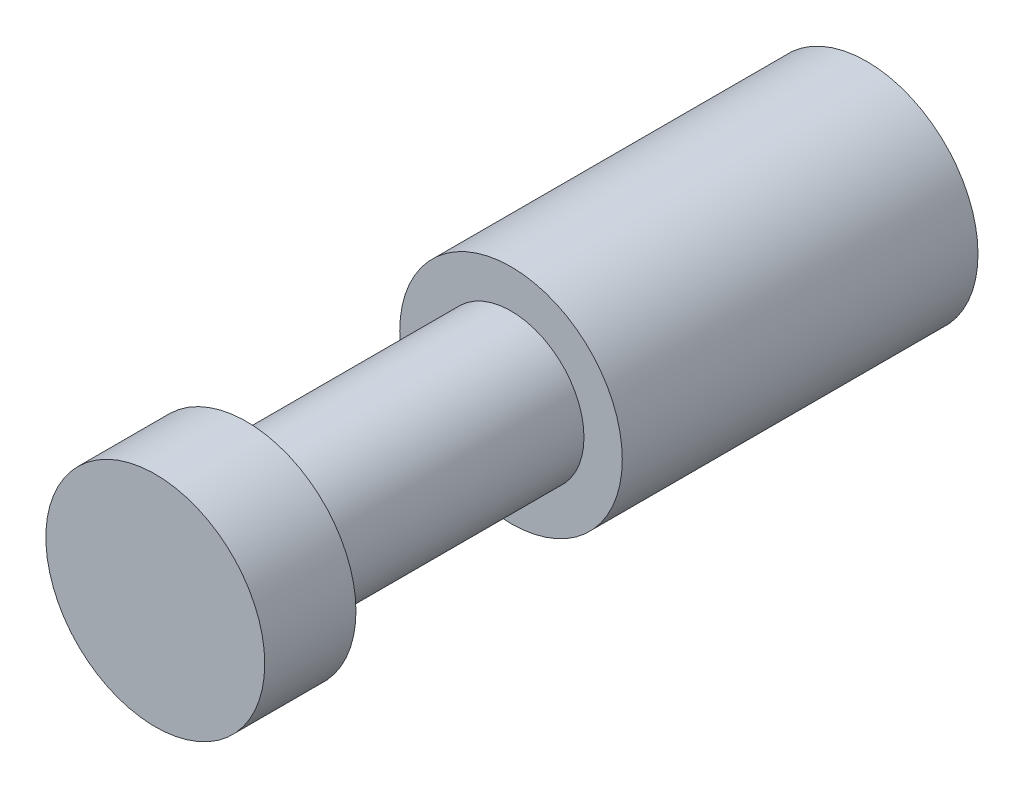
SolidWorks part; units mm, degrees
ref_plane "Front Plane" through (0, 0, 0) normal (0, 0, 1) x (1, 0, 0)
ref_plane "Top Plane" through (0, 0, 0) normal (0, 1, 0) x (1, 0, 0)
ref_plane "Right Plane" through (0, 0, 0) normal (1, 0, 0) x (0, 0, -1)
sketch "Sketch1" plane through (0, 0, 0) normal (0, 0, 1) x (1, 0, 0)
  circle A0 centre (0, 0) radius 4.25
  circle A1 centre (0, 0) radius 6.1
  dimension "D1" = 8.5
  dimension "D2" = 12.2
extrude "Boss-Extrude1" add sketch "Sketch1" along normal blind 12
sketch "Sketch2" plane through (0, 0, 12) normal (0, 0, 1) x (1, 0, 0)
  circle A0 centre (0, 0) radius 6.1
  circle A1 centre (0, 0) radius 6.1 construction
  dimension "D1" = 0
extrude "Boss-Extrude2" add sketch "Sketch2" along normal blind 2
sketch "Sketch3" plane through (0, 0, 14) normal (0, 0, 1) x (1, 0, 0)
  circle A0 centre (0, 0) radius 4
  dimension "D1" = 8
extrude "Boss-Extrude3" add sketch "Sketch3" along normal blind 20
sketch "Sketch4" plane through (0, 0, 34) normal (0, 0, 1) x (1, 0, 0)
  circle A0 centre (0, 0) radius 6
  dimension "D1" = 12
extrude "Boss-Extrude4" add sketch "Sketch4" along normal blind 5
sketch "Sketch5" plane through (0, 0, 14) normal (0, 0, 1) x (1, 0, 0)
  circle A0 centre (0, 0) radius 6.1
  circle A1 centre (0, 0) radius 6.1 construction
extrude "Boss-Extrude5" add sketch "Sketch5" along normal blind 5.5
